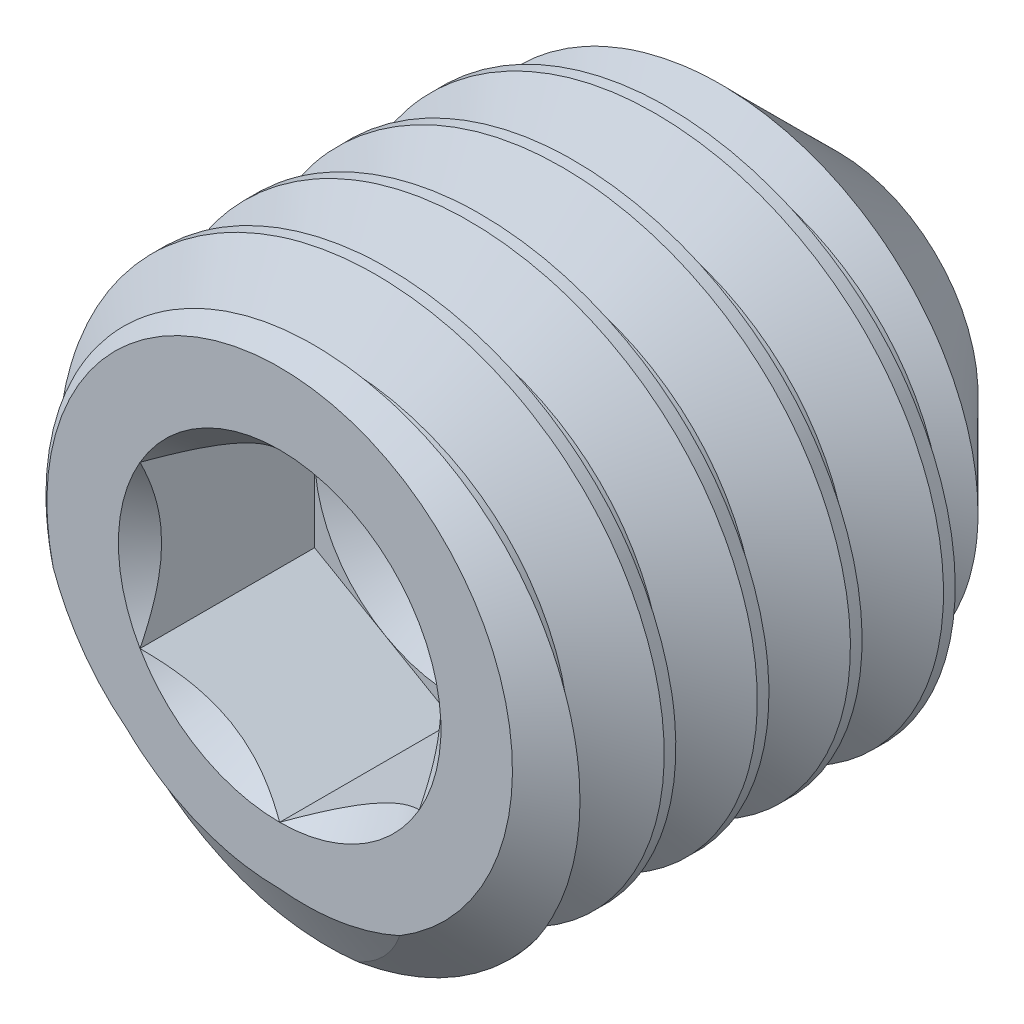
SolidWorks part; units mm, degrees
other "Imported1" parameters "D3"=3.3, "D1"=46.842, "Length"=3, "Drive Size"=1.5, "Thread Size"=3, "Thread Pitch"=0.5, "hex Depth"=0.9375, "D2"=0.9112, "Dia"=12, "D4"=2.3829, "Cup Point Dia"=3.3528, "D5"=1.436, "D6"=1.4986, "D7"=5.0014, "Pitch"=1.75
ref_plane "Front" through (0, 0, 0) normal (0, 0, 1) x (1, 0, 0)
ref_plane "Top" through (0, 0, 0) normal (0, 1, 0) x (1, 0, 0)
ref_plane "Right" through (0, 0, 0) normal (1, 0, 0) x (0, 0, -1)
sketch "Sketch1" plane through (0, 0, 0) normal (1, 0, 0) x (0, 0, -1)
  line L0 (1.5, 1.5) -> (-1.5, 1.5) construction
  line L1 (-1.5, 1.5) -> (-1.5, -1.5) construction
  line L2 (-1.5, -1.5) -> (1.5, -1.5) construction
  line L3 (1.5, -1.5) -> (1.5, 1.5) construction
  line L4 (-1.5, 0.75) -> (-1.5, -0.75) construction
  line L5 (1.4688, 1.5541) -> (1.9688, 1.5541) construction
  line L6 (1.9688, 1.5541) -> (1.7188, 1.1211) construction
  line L7 (1.7188, 1.1211) -> (1.4688, 1.5541) construction
  line L8 (1.4844, 1.5271) -> (1.9531, 1.5271) construction
  line L9 (1.5, 1.5) -> (1.9375, 1.5) construction
  line L10 (1.7188, 1.5541) -> (1.7188, 1.5) construction
  line L11 (1.6875, 1.1752) -> (1.75, 1.1752) construction
  line L12 (1.7188, 1.1752) -> (1.7188, 1.1211) construction
  point P3 (0, 1.5)
  point P19 (1.7188, 1.5271)
  point P24 (-1.5, 0)
  point P25 (-1.5, 0)
  dimension "D1" = 0.0625
sketch "Sketch11" plane through (0, 0, 0) normal (1, 0, 0) x (0, 0, -1)
  line L0 (-1.5, 0) -> (-1.5, 1.25)
  line L1 (-1.5, 1.25) -> (-1.3249, 1.5)
  line L2 (-1.3249, 1.5) -> (0.75, 1.5)
  line L3 (0.75, 1.5) -> (1.5, 0.75)
  line L4 (1.5, 0.75) -> (1.0494, 0)
  line L5 (1.0494, 0) -> (-1.5, 0)
  line L6 (1.0494, 0) -> (1.5, 0) construction
  line L7 (1.5, 0) -> (1.5, 0.75) construction
  line L8 (1.5, -0.75) -> (1.0494, 0) construction
  line L9 (-1.3249, -1.5) -> (0.75, -1.5) construction
  line L10 (-1.5, -1.5) -> (1.5, -1.5) construction
  line L11 (-1.5, 1.5) -> (-1.5, -1.5) construction
  line L12 (1.5, -1.5) -> (1.5, 1.5) construction
  point P11 (-0.25, -1.5)
  point P12 (-1.5, 1.5)
  dimension "D3" = 35
  dimension "D5" = 118
  dimension "D6" = 45
  dimension "D1" = 0.25
  dimension "D2" = 1.75
  dimension "D4" = 0.75
revolve "Revolve1" add sketch "Sketch11" angle 360 about L6
sketch "Sketch2" plane through (0, 0, 1.5) normal (0, 0, 1) x (1, 0, 0)
  line L1 (0, 0.866) -> (-0.75, 0.433)
  line L2 (-0.75, 0.433) -> (-0.75, -0.433)
  line L3 (-0.75, -0.433) -> (0, -0.866)
  line L4 (0, -0.866) -> (0.75, -0.433)
  line L5 (0.75, -0.433) -> (0.75, 0.433)
  line L6 (0.75, 0.433) -> (0, 0.866)
  circle A0 centre (0, 0) radius 0.75 construction
  circle A1 centre (0, 0) radius 1.5 construction
extrude "Cut-Extrude1" cut sketch "Sketch2" against normal blind 0.9375
sketch "Sketch3" plane through (0, 0, 1.5) normal (0, 0, 1) x (1, 0, 0)
  circle A0 centre (0, 0) radius 0.866
extrude "Cut-Extrude2" cut sketch "Sketch3" against normal through all draft 45
sketch "Sketch4" plane through (0, 0, 0.5625) normal (0, 0, 1) x (1, 0, 0)
  circle A0 centre (0, 0) radius 0.75 construction
  circle A1 centre (0, 0) radius 0.75
extrude "Cut-Extrude3" cut sketch "Sketch4" against normal through all draft 60
sketch "Sketch13" plane through (0, 0, 0) normal (1, 0, 0) x (0, 0, -1)
  line L0 (0, -1.5) -> (0, 1.5) construction
  line L2 (-1.3249, 1.5) -> (0.75, 1.5) construction
  line L4 (1.0494, 0) -> (-1.5, 0) construction
  point P0 (-1.9506, 0)
  point P4 (0, 0)
  point P9 (1.9506, 0)
  dimension "D1" = 3
ref_plane "Plane1" through (0, 0, -1.5) normal (0, 0, 1) x (1, 0, 0)
sketch "Sketch5" plane through (0, 0, -1.5) normal (0, 0, 1) x (1, 0, 0)
  circle A0 centre (0, 0) radius 1.5 construction
  circle A1 centre (0, 0) radius 1.5
curve "Helix/Spiral1" pitch 0.5 height 3.3 radius 1.5 centre (0, 0, -1.5) axis (0, 0, 1) start towards (0, 1, 0)
sketch "Sketch6" plane through (0, 0, 0) normal (1, 0, 0) x (0, 0, -1)
  line L0 (1.4687, 1.5541) -> (1.9687, 1.5541) construction
  line L1 (1.9687, 1.5541) -> (1.7187, 1.1211) construction
  line L2 (1.7187, 1.1211) -> (1.4687, 1.5541) construction
  line L3 (1.7187, 1.5541) -> (1.7187, 1.5) construction
  line L4 (1.5, 1.5) -> (1.9375, 1.5) construction
  line L5 (1.7187, 1.1752) -> (1.7187, 1.1211) construction
  line L6 (1.6875, 1.1752) -> (1.4844, 1.5271)
  line L7 (1.4844, 1.5271) -> (1.9531, 1.5271)
  line L8 (1.4844, 1.5271) -> (1.9531, 1.5271) construction
  line L10 (1.6875, 1.1752) -> (1.75, 1.1752) construction
  line L12 (1.75, 1.1752) -> (1.6875, 1.1752)
  line L13 (1.9531, 1.5271) -> (1.75, 1.1752)
  point P9 (1.7187, 1.5)
  point P14 (1.7187, 1.5271)
  point P15 (1.7187, 1.5271)
  point P16 (1.7187, 1.1752)
  dimension "D1" = 0.5
  dimension "D2" = 0.0625
sweep "Cut-Sweep1" cut profiles "Sketch6" path "Helix/Spiral1"
equation "\"D3@Helix/Spiral1\" = \"Length@Sketch1\" * 1.1"
equation "\"hex Depth@Cut-Extrude1\" = \"Drive Size@Sketch1\" * .625"
equation "\"D1@Sketch6\" = \"Thread Pitch@Sketch1\""
equation "\"D2@Sketch6\" = \"D1@Sketch6\" / 8"
equation "\"D1@Sketch11\" = \"Thread Pitch@Sketch1\" * .5"
equation "\"D2@Sketch11\" = \"Thread Pitch@Sketch1\" * 3.5"
equation "\"D1@Helix/Spiral1\" = \"Thread Pitch@Sketch1\""
equation "\"D4@Sketch11\" = \"Thread Pitch@Sketch1\" * 1.5"
equation "\"D1@Sketch1\" = \"Thread Pitch@Sketch1\" / 8"
equation "\"D1@Sketch13\"=\"Thread Size@Sketch1\""
